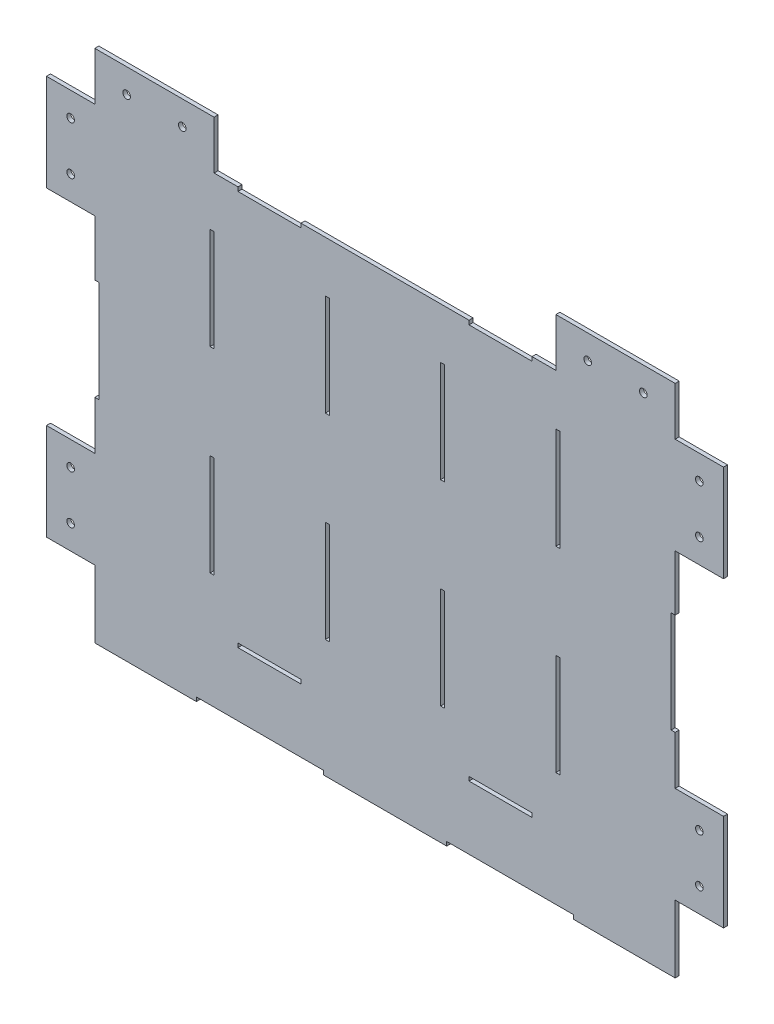
SolidWorks part; units mm, degrees
material "6061-T6 (SS)"
ref_plane "X-Y Datum" through (0, 0, 0) normal (0, 0, 1) x (1, 0, 0)
ref_plane "X-Z Datum" through (0, 0, 0) normal (0, 1, 0) x (1, 0, 0)
ref_plane "Y-Z Datum" through (0, 0, 0) normal (1, 0, 0) x (0, 0, -1)
sketch "Sketch1" plane through (0, 0, 0) normal (0, 0, 1) x (1, 0, 0)
  line L0 (-228.6115, 0) -> (228.6115, 0) construction
  line L1 (-228.6115, -157.216) -> (228.6115, -157.216)
  line L2 (-228.6115, -157.216) -> (-228.6115, 157.216)
  line L3 (-228.6115, 157.216) -> (228.6115, 157.216)
  line L4 (228.6115, -157.216) -> (228.6115, 157.216)
  line L5 (-228.6115, -157.216) -> (228.6115, 157.216) construction
  line L6 (-228.6115, 157.216) -> (228.6115, -157.216) construction
  line L8 (-228.6115, 0) -> (-134.6215, 0) construction
  line L9 (-225.4325, -154.041) -> (-225.4325, 154.041)
  line L10 (-224.4165, -153.025) -> (-138.8165, -153.025) construction
  line L15 (-224.4165, -153.025) -> (-224.4165, 153.025) construction
  line L16 (-224.4165, 153.025) -> (-138.8165, 153.025) construction
  line L17 (-138.8165, -153.025) -> (-138.8165, 153.025) construction
  line L18 (-224.4165, -153.025) -> (-138.8165, 153.025) construction
  line L19 (-224.4165, 153.025) -> (-138.8165, -153.025) construction
  line L20 (-225.4325, 154.041) -> (-137.8005, 154.041)
  line L21 (-137.8005, -154.041) -> (-137.8005, 154.041)
  line L22 (-225.4325, -154.041) -> (-137.8005, -154.041)
  line L26 (-134.6255, 154.041) -> (-46.9935, 154.041)
  line L27 (-133.6095, -153.025) -> (-48.0095, -153.025) construction
  line L28 (-133.6095, -153.025) -> (-133.6095, 153.025) construction
  line L29 (-133.6095, 153.025) -> (-48.0095, 153.025) construction
  line L30 (-48.0095, -153.025) -> (-48.0095, 153.025) construction
  line L31 (-133.6095, -153.025) -> (-48.0095, 153.025) construction
  line L32 (-133.6095, 153.025) -> (-48.0095, -153.025) construction
  line L33 (-46.9935, -154.041) -> (-46.9935, 154.041)
  line L34 (-134.6255, -154.041) -> (-46.9935, -154.041)
  line L35 (-134.6255, -154.041) -> (-134.6255, 154.041)
  line L36 (42.7975, -153.025) -> (42.7975, 153.025) construction
  line L37 (43.8135, -154.041) -> (43.8135, 154.041)
  line L38 (-42.8025, -153.025) -> (42.7975, 153.025) construction
  line L39 (-42.8025, 153.025) -> (42.7975, -153.025) construction
  line L40 (-42.8025, -153.025) -> (-42.8025, 153.025) construction
  line L41 (-43.8185, -154.041) -> (-43.8185, 154.041)
  line L42 (-42.8025, 153.025) -> (42.7975, 153.025) construction
  line L43 (-43.8185, 154.041) -> (43.8135, 154.041)
  line L44 (-42.8025, -153.025) -> (42.7975, -153.025) construction
  line L45 (-43.8185, -154.041) -> (43.8135, -154.041)
  line L46 (133.6045, -153.025) -> (133.6045, 153.025) construction
  line L47 (134.6205, -154.041) -> (134.6205, 154.041)
  line L48 (48.0045, -153.025) -> (133.6045, 153.025) construction
  line L49 (48.0045, 153.025) -> (133.6045, -153.025) construction
  line L50 (48.0045, -153.025) -> (48.0045, 153.025) construction
  line L51 (46.9885, -154.041) -> (46.9885, 154.041)
  line L52 (48.0045, 153.025) -> (133.6045, 153.025) construction
  line L53 (46.9885, 154.041) -> (134.6205, 154.041)
  line L54 (48.0045, -153.025) -> (133.6045, -153.025) construction
  line L55 (46.9885, -154.041) -> (134.6205, -154.041)
  line L56 (224.4115, -153.025) -> (224.4115, 153.025) construction
  line L57 (225.4275, -154.041) -> (225.4275, 154.041)
  line L58 (138.8115, -153.025) -> (224.4115, 153.025) construction
  line L59 (138.8115, 153.025) -> (224.4115, -153.025) construction
  line L60 (138.8115, -153.025) -> (138.8115, 153.025) construction
  line L61 (137.7955, -154.041) -> (137.7955, 154.041)
  line L62 (138.8115, 153.025) -> (224.4115, 153.025) construction
  line L63 (137.7955, 154.041) -> (225.4275, 154.041)
  line L64 (138.8115, -153.025) -> (224.4115, -153.025) construction
  line L65 (137.7955, -154.041) -> (225.4275, -154.041)
  line L67 (-228.6115, -157.216) -> (225.4365, -157.216)
  line L71 (-228.6115, -157.216) -> (228.6115, -157.216)
  line L74 (-225.4365, -157.216) -> (225.4365, -157.216)
  line L75 (-225.4365, -157.216) -> (-225.4365, -208.106)
  line L76 (-225.4365, -208.106) -> (225.4365, -208.106)
  line L77 (225.4365, -157.216) -> (225.4365, -208.106)
  line L79 (-228.6115, -157.216) -> (228.6115, -157.216)
  line L80 (-228.6115, -157.216) -> (-228.6115, -210.392)
  line L81 (-228.6115, -210.392) -> (228.6115, -210.392)
  line L82 (228.6115, -157.216) -> (228.6115, -210.392)
  point P0 (0, 0)
  point P10 (-181.6165, 0)
  point P22 (-90.8095, 0)
  dimension "D1" = 314.432
  dimension "D2" = 457.223
  dimension "D4" = 1.016
  dimension "D5" = 3.179
  dimension "D6" = 3.175
  dimension "D7" = 1.016
  dimension "D8" = 90.807
  dimension "D9" = 3.175
  dimension "D11" = 3.175
  dimension "D12" = 50.89
  dimension "D13" = 2.286
  dimension "D14" = 3.175
  dimension "D15" = 3.175
  dimension "D10" = 4
extrude "Boss-Extrude2" add sketch "Sketch1" along normal blind 3.175 contours L61 L65 L57 L63 | L51 L55 L47 L53 | L41 L45 L37 L43 | L35 L34 L33 L26 | L9 L22 L21 L20 | L1 L71 L4 L3 L2 L65 L61 L63 L57 L55 L51 L53 L47 L45 L41 L43 L37 L22 L9 L20 L21 L34 L35 L26 L33 | L77 L71 L75 L76 | L82 L1 L77 L76 L75 L80 L81 region at (-228.0566, 0, 0) region at (-227.024, -161.819, 0) region at (0, -182.661, 0) region at (-181.6165, 0, 0) region at (-90.8095, 0, 0) region at (-0.0025, 0, 0) region at (90.8045, 0, 0) region at (181.6115, 0, 0)
sketch "Sketch4" plane through (0, 0, 3.175) normal (0, 0, 1) x (1, 0, 0)
  line L0 (-136.213, 117.216) -> (-136.213, 157.216) construction
  line L1 (-228.6115, 157.216) -> (228.6115, 157.216) construction
  line L2 (-228.6115, 157.216) -> (228.6115, 157.216) construction
  line L5 (-134.6255, -154.041) -> (-134.6255, 154.041) construction
  line L6 (-137.8005, 37.216) -> (-134.6255, 37.216)
  line L7 (-137.8005, 37.216) -> (-137.8005, 117.216)
  line L8 (-137.8005, 117.216) -> (-134.6255, 117.216)
  line L9 (-134.6255, 37.216) -> (-134.6255, 117.216)
  line L10 (-137.8005, 37.216) -> (-134.6255, 117.216) construction
  line L11 (-137.8005, 117.216) -> (-134.6255, 37.216) construction
  line L13 (-45.406, 153.025) -> (-45.406, -157.216) construction
  line L14 (-228.6115, -157.216) -> (228.6115, -157.216) construction
  dimension "D1" = 40
  dimension "D2" = 3.175
  dimension "D3" = 80
  dimension "D4" = 90.807
extrude "Cut-Extrude1" cut sketch "Sketch4" against normal blind 3.175 contours L6 L9 L8 L7 region at (-136.213, 77.216, 3.175)
mirror "Mirror1" about plane through (0, 0, 0) normal (0, 1, 0) of "Cut-Extrude1"
pattern_linear "LPattern1" count 4 spacing 90.807 along (1, 0, 0) of "Mirror1"
sketch "Sketch5" plane through (0, 0, 3.175) normal (0, 0, 1) x (1, 0, 0)
  line L0 (-225.4365, -157.216) -> (-228.6115, -157.216)
  line L1 (-225.4325, -154.041) -> (-228.6115, -154.041)
  line L2 (-228.6115, -157.216) -> (-228.6115, 157.216) construction
  line L3 (-228.6115, -154.041) -> (-228.6115, -157.216)
  line L4 (-228.6115, -155.6285) -> (-194.996, -155.6285)
  line L5 (-194.996, -155.6285) -> (-91.0201, -155.6285) construction
  line L6 (-225.4325, -154.041) -> (-137.8005, -154.041) construction
  line L7 (-115.8495, -157.216) -> (-66.1907, -157.216)
  line L8 (-115.8495, -157.216) -> (-115.8495, -154.041)
  line L9 (-115.8495, -154.041) -> (-66.1907, -154.041)
  line L10 (-66.1907, -157.216) -> (-66.1907, -154.041)
  line L11 (-115.8495, -157.216) -> (-66.1907, -154.041) construction
  line L12 (-115.8495, -154.041) -> (-66.1907, -157.216) construction
  dimension "D1" = 112.762
  dimension "D2" = 49.6588
extrude "Cut-Extrude2" cut sketch "Sketch5" against normal blind 3.175 contours L7 L10 L9 L8 region at (-91.0201, -155.6285, 3.175)
mirror "Mirror2" about plane through (0, 0, 0) normal (1, 0, 0) of "Cut-Extrude2"
mirror "Mirror3" about plane through (0, 0, 0) normal (0, 1, 0) of "Mirror2"
sketch "Sketch6" plane through (0, 0, 3.175) normal (0, 0, 1) x (1, 0, 0)
  line L0 (-228.6115, -210.392) -> (-228.6115, 157.216) construction
  line L3 (-228.6115, 157.216) -> (-115.8495, 157.216) construction
  line L5 (-225.4365, 157.216) -> (-228.6115, 157.216)
  line L6 (-227.024, 157.216) -> (-227.024, 37.216) construction
  line L7 (-227.024, 37.216) -> (-227.024, -42.784) construction
  line L9 (-225.4365, -42.784) -> (-228.6115, -42.784)
  line L10 (-225.4365, -42.784) -> (-225.4365, 37.216)
  line L11 (-225.4365, 37.216) -> (-228.6115, 37.216)
  line L12 (-228.6115, -42.784) -> (-228.6115, 37.216)
  line L13 (-225.4365, -42.784) -> (-228.6115, 37.216) construction
  line L14 (-225.4365, 37.216) -> (-228.6115, -42.784) construction
  point P11 (-227.024, -2.784)
  dimension "D1" = 3.175
  dimension "D2" = 120
  dimension "D3" = 80
extrude "Cut-Extrude3" cut sketch "Sketch6" against normal through all contours L12 L9 L10 L11 region at (-227.024, -2.784, 3.175)
mirror "Mirror5" about plane through (0, 0, 0) normal (1, 0, 0) of "Cut-Extrude3"
sketch "Sketch7" plane through (0, 0, 3.175) normal (0, 0, 1) x (1, 0, 0)
  line L1 (-228.6115, -210.392) -> (-228.6115, -42.784) construction
  line L5 (-148.6115, -210.392) -> (-48.6115, -210.392)
  line L6 (-148.6115, -210.392) -> (-148.6115, -207.217)
  line L7 (-148.6115, -207.217) -> (-48.6115, -207.217)
  line L8 (-48.6115, -210.392) -> (-48.6115, -207.217)
  line L9 (-148.6115, -210.392) -> (-48.6115, -207.217) construction
  line L10 (-148.6115, -207.217) -> (-48.6115, -210.392) construction
  point P7 (-98.6115, -208.8045)
  dimension "D1" = 80
  dimension "D2" = 100
  dimension "D3" = 3.175
extrude "Cut-Extrude4" cut sketch "Sketch7" against normal blind 3.175 contours L5 L8 L7 L6 region at (-98.6115, -208.8045, 3.175)
mirror "Mirror6" about plane through (0, 0, 0) normal (1, 0, 0) of "Cut-Extrude4"
sketch "Sketch8" plane through (0, 0, 0) normal (0, 0, -1) x (-1, 0, 0)
  line L0 (-228.6115, -210.392) -> (-228.6115, -42.784) construction
  line L1 (-228.6115, 157.216) -> (-266.7115, 157.216)
  line L2 (-228.6115, 157.216) -> (-228.6115, 81.016)
  line L3 (-228.6115, 81.016) -> (-266.7115, 81.016)
  line L4 (-266.7115, 157.216) -> (-266.7115, 81.016)
  line L5 (-228.6115, -157.2452) -> (-266.7115, -157.2452)
  line L6 (-228.6115, -157.2452) -> (-228.6115, -81.0452)
  line L7 (-228.6115, -81.0452) -> (-266.7115, -81.0452)
  line L8 (-266.7115, -157.2452) -> (-266.7115, -81.0452)
  line L9 (-247.6615, 157.216) -> (-247.6615, 81.016) construction
  line L10 (-247.6615, -81.0452) -> (-247.6615, -157.2452) construction
  line L11 (-266.7115, 119.116) -> (-228.6115, 119.116) construction
  line L12 (-247.6615, 157.216) -> (-247.6615, 119.116) construction
  line L13 (-250.6615, 138.166) -> (-250.6615, 119.116) construction
  line L14 (-148.6115, -210.392) -> (-228.6115, -210.392) construction
  line L15 (-247.6615, -81.0452) -> (-247.6615, -119.1452) construction
  line L16 (-181.6215, 195.316) -> (-181.6215, 157.216) construction
  line L17 (-228.6115, 157.216) -> (-134.6315, 157.216)
  line L18 (-228.6115, 157.216) -> (-228.6115, 195.316)
  line L19 (-228.6115, 195.316) -> (-134.6315, 195.316)
  line L20 (-134.6315, 157.216) -> (-134.6315, 195.316)
  line L21 (-228.6115, 176.266) -> (-134.6315, 176.266) construction
  line L22 (-159.714, 179.266) -> (-134.6315, 179.266) construction
  circle A1 centre (-247.6615, 138.166) radius 3
  circle A2 centre (-247.6615, 100.066) radius 3
  circle A3 centre (-247.6615, -100.0952) radius 3
  circle A4 centre (-247.6615, -138.1952) radius 3
  circle A5 centre (-203.529, 176.266) radius 3
  circle A6 centre (-159.714, 176.266) radius 3
  dimension "D1" = 76.2
  dimension "D2" = 16.05
  dimension "D4" = 6
  dimension "D5" = 19.05
  dimension "D7" = 38.1
  dimension "D8" = 53.1468
  dimension "D9" = 6
  dimension "D13" = 43.815
  dimension "D3" = 19.05
  dimension "D6" = 19.05
  dimension "D10" = 19.05
  dimension "D11" = 16.05
  dimension "D12" = 93.98
extrude "Boss-Extrude3" add sketch "Sketch8" against normal blind 3.175 contours L1 L4 L3 L2 A1 A2 | L17 L20 L19 L18 A5 A6 | L8 L5 L6 L7 A3 A4 region at (247.6615, 119.116, 0) region at (181.6215, 176.266, 0) region at (247.6615, -119.1452, 0)
mirror "Mirror7" about plane through (0, 0, 0) normal (1, 0, 0) of "Boss-Extrude3"
